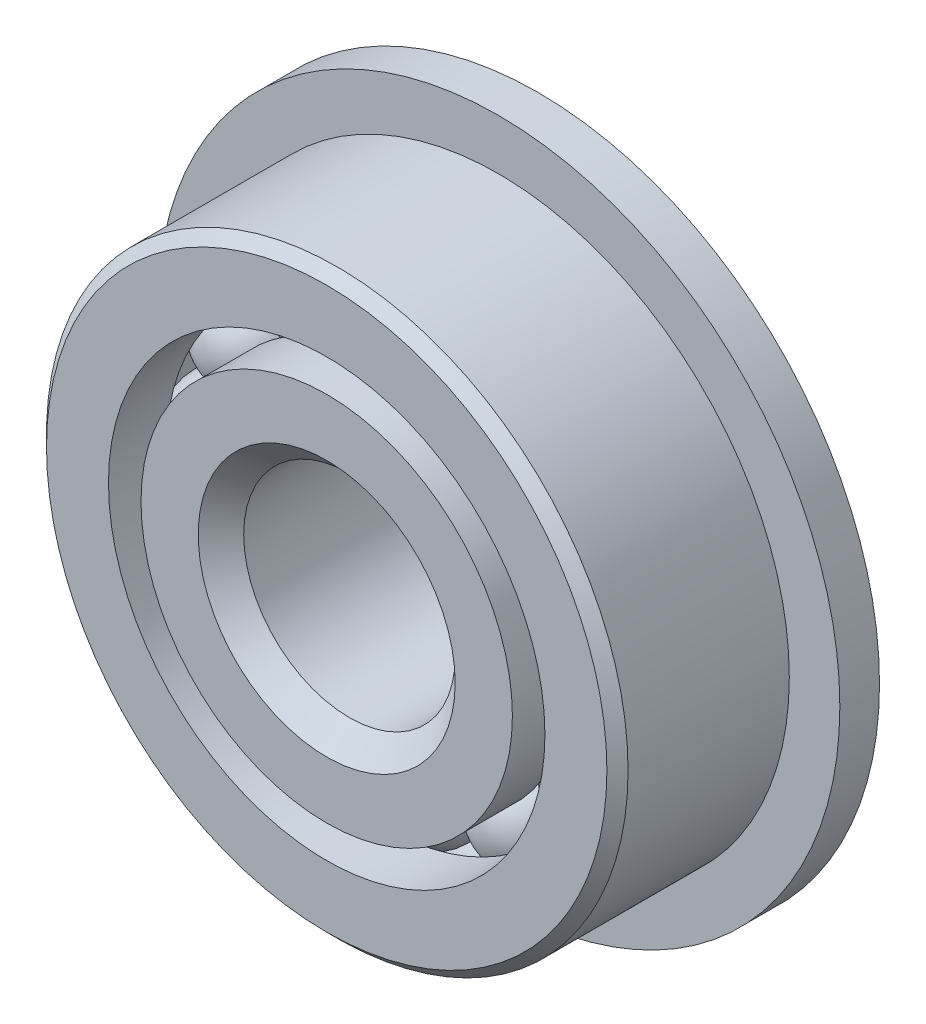
SolidWorks part; units mm, degrees
ref_plane "Front Plane" through (0, 0, 0) normal (0, 0, 1) x (1, 0, 0)
ref_plane "Top Plane" through (0, 0, 0) normal (0, 1, 0) x (1, 0, 0)
ref_plane "Right Plane" through (0, 0, 0) normal (1, 0, 0) x (0, 0, -1)
sketch "Sketch1" plane through (0, 0, 0) normal (1, 0, 0) x (0, 0, -1)
  line L0 (-3.175, 0) -> (3.175, 0) construction
  line L1 (0, 8.7312) -> (0, -8.7312) construction
  line L2 (2.8575, 8.7312) -> (-2.8575, 8.7312)
  line L3 (-2.8575, 8.7312) -> (-3.175, 8.4138)
  line L4 (-3.175, 8.4138) -> (-3.175, 6.5527)
  line L5 (-3.175, 6.5527) -> (-1.4436, 6.5527)
  line L6 (3.175, 6.5527) -> (1.4436, 6.5527)
  line L7 (3.175, 8.4138) -> (3.175, 6.5527)
  line L8 (2.8575, 8.7312) -> (3.175, 8.4138)
  line L9 (0, 8.7312) -> (0, 6.0643) construction
  line L11 (3.175, 0) -> (4.7625, 0) construction
  arc A0 (-1.4436, 6.5527) -> (1.4436, 6.5527) centre (0, 6.0643) cw
  circle A1 centre (0, 6.0643) radius 1.524 construction
  point P14 (0, 3.175)
  dimension "D3" = 3.048
  dimension "D1" = 45
  dimension "Width" = 6.35
  dimension "OD" = 17.4625
  dimension "D2" = 0.3175
  dimension "Shaft Dia" = 6.35
  dimension "D4" = 0.4885
  dimension "D5" = 2.667
  dimension "Total Wd" = 7.9375
revolve "Revolve1" add sketch "Sketch1" angle 360 about L0
sketch "Sketch2" plane through (0, 0, 0) normal (1, 0, 0) x (0, 0, -1)
  line L0 (-3.175, 5.5758) -> (-1.4436, 5.5758)
  line L1 (-3.175, 8.4138) -> (-3.175, -8.4138) construction
  line L2 (-3.175, 5.5758) -> (-3.175, 4.7167)
  line L3 (-3.175, 4.7167) -> (-2.3159, 3.8576)
  line L4 (-2.3159, 3.8576) -> (0, 3.8576)
  line L5 (0, 8.7312) -> (0, -8.7312) construction
  line L6 (0, 3.8576) -> (0, 4.5403)
  line L7 (0, 4.5403) -> (0, 3.175) construction
  line L8 (-3.175, 5.5758) -> (-3.175, 3.8576) construction
  line L9 (-3.175, 3.8576) -> (-2.3159, 3.8576) construction
  arc A0 (-1.4436, 5.5758) -> (0, 4.5403) centre (0, 6.0643) ccw
  arc A1 (1.4436, 6.5527) -> (-1.4436, 6.5527) centre (0, 6.0643) ccw construction
  circle A2 centre (0, 6.0643) radius 1.524 construction
  dimension "D1" = 45
revolve "Revolve2" add sketch "Sketch2" angle 360 about L0
sketch "Sketch3" plane through (0, 0, 0) normal (1, 0, 0) x (0, 0, -1)
  line L0 (-3.175, 4.7167) -> (-2.3159, 3.8576)
  line L1 (-2.3159, 3.8576) -> (0, 3.8576)
  line L2 (0, 3.8576) -> (0, 4.5403)
  line L3 (-3.175, 4.7167) -> (-3.175, 3.8576)
  line L4 (-3.175, 5.5758) -> (-3.175, 3.8576) construction
  line L5 (-3.175, 3.8576) -> (-2.4924, 3.175)
  line L6 (-2.4924, 3.175) -> (4.445, 3.175)
  line L8 (4.445, 3.175) -> (4.7625, 3.4925)
  line L10 (4.7625, 3.4925) -> (4.7625, 5.5758)
  line L11 (4.7625, 5.5758) -> (1.4436, 5.5758)
  line L13 (2.8575, 8.7312) -> (3.175, 8.4138) construction
  circle A0 centre (0, 6.0643) radius 1.524 construction
  arc A1 (1.4436, 5.5758) -> (0, 4.5403) centre (0, 6.0643) cw
revolve "Revolve3" add sketch "Sketch3" angle 360 about L0
sketch "Sketch4" plane through (0, 0, 0) normal (1, 0, 0) x (0, 0, -1)
  line L0 (-1.524, 6.0643) -> (1.524, 6.0643)
  circle A1 centre (0, 6.0643) radius 1.524 construction
  arc A2 (-1.524, 6.0643) -> (1.524, 6.0643) centre (0, 6.0643) cw
  arc A3 (1.4436, 6.5527) -> (-1.4436, 6.5527) centre (0, 6.0643) ccw construction
revolve "Revolve4" add sketch "Sketch4" angle 360 about L0
ref_axis "Axis1" through (0, 0, -3.175) along (0, 0, 1)
pattern_circular "CirPattern1" count 12 over 360 about axis through (0, 0, -3.175) along (0, 0, 1) of bodies 104
sketch "Sketch5" plane through (0, 0, 0) normal (1, 0, 0) x (0, 0, -1)
  line L0 (3.175, 8.4138) -> (3.175, 6.5527) construction
  line L1 (3.175, 7.4832) -> (1.9844, 7.4832)
  line L2 (3.175, 7.4832) -> (3.175, 10.2489)
  line L3 (3.175, 10.2489) -> (1.9844, 10.2489)
  line L4 (1.9844, 7.4832) -> (1.9844, 10.2489)
  line L5 (4.7625, 0) -> (-3.175, 0) construction
  dimension "Flange Thickness" = 1.1906
  dimension "Flange OD" = 20.4978
revolve "Revolve5" add sketch "Sketch5" angle 360 about L5
equation "\"D2@Sketch1\" = \"Width@Sketch1\"*.05"
equation "\"D4@Sketch1\" = (((\"OD@Sketch1\"-\"Width@Sketch1\")/2)/3.25)/3.5"
equation "\"D2@CirPattern1\" = 360/\"Balls@CirPattern1\""
equation "\"D5@Sketch1\" = \"D3@Sketch1\" * 7/8"
